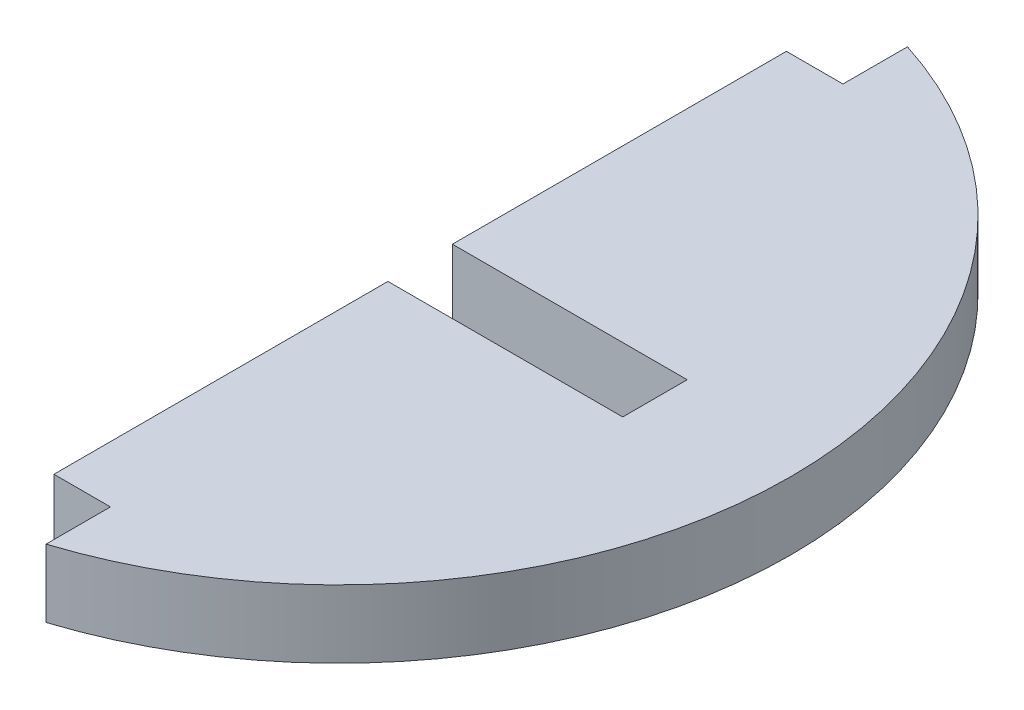
SolidWorks part; units mm, degrees
ref_plane "Front Plane" through (0, 0, 0) normal (0, 0, 1) x (1, 0, 0)
ref_plane "Top Plane" through (0, 0, 0) normal (0, 1, 0) x (1, 0, 0)
ref_plane "Right Plane" through (0, 0, 0) normal (1, 0, 0) x (0, 0, -1)
sketch "Sketch1" plane through (0, 0, 0) normal (0, 1, 0) x (1, 0, 0)
  line L0 (-20, 0) -> (20, 0) construction
  line L1 (-20, 0) -> (20, 0) construction
  line L2 (0, -20) -> (0, 20) construction
  line L4 (3.6213, -1.425) -> (14, -1.425)
  line L5 (14, -1.425) -> (14, 1.425)
  line L6 (14, 1.425) -> (3.6213, 1.425)
  line L9 (6.1213, -19.0402) -> (6.1213, -16.1902)
  line L10 (6.1213, -16.1902) -> (3.6213, -16.1902)
  line L11 (3.6213, -16.1902) -> (3.6213, -1.425)
  line L12 (6.1213, 19.0402) -> (6.1213, 16.1902)
  line L13 (6.1213, 16.1902) -> (3.6213, 16.1902)
  line L14 (3.6213, 16.1902) -> (3.6213, 1.425)
  arc A0 (6.1213, -19.0402) -> (6.1213, 19.0402) centre (0, 0) ccw
  point P4 (0, 0)
  point P5 (14, 0)
  dimension "D1" = 2.85
  dimension "D2" = 2.5
extrude "Boss-Extrude1" add sketch "Sketch1" along normal blind 1.5 and the other way blind 1.5
